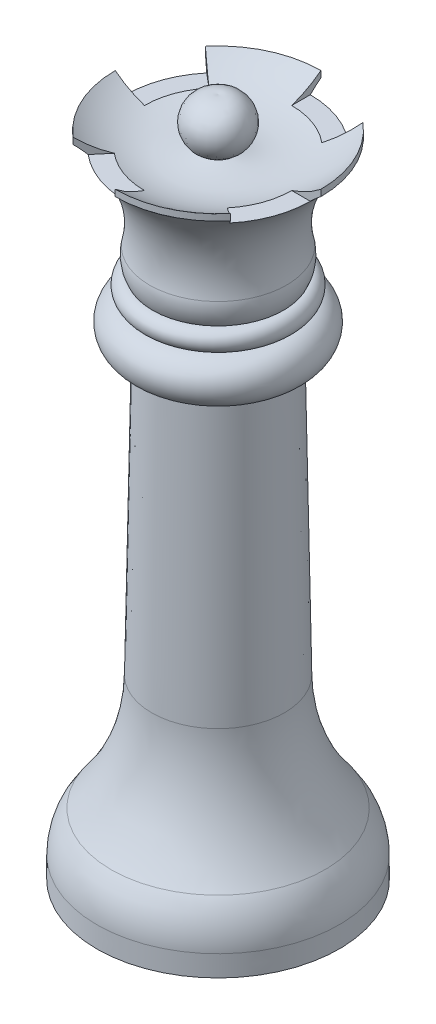
SolidWorks part; units mm, degrees
material "PVC Rigid"
ref_plane "Front Plane" through (0, 0, 0) normal (0, 0, 1) x (1, 0, 0)
ref_plane "Top Plane" through (0, 0, 0) normal (0, 1, 0) x (1, 0, 0)
ref_plane "Right Plane" through (0, 0, 0) normal (1, 0, 0) x (0, 0, -1)
sketch "Sketch1" plane through (0, 0, 0) normal (0, 0, 1) x (1, 0, 0)
  line L0 (0, 0) -> (-11.6, 0)
  line L3 (-11.5897, 2) -> (-11.6, 0)
  line L32 (0, 65) -> (0, 0)
  line L33 (-5.8734, 44.12) -> (-6.3432, 44.12)
  line L34 (-6.3432, 16.936) -> (-5.8734, 44.12)
  line L35 (-9.8373, 61.4466) -> (-9.8373, 62.061)
  line L36 (0, 0) -> (0, 50) construction
  arc A0 (-10.2296, 5.8838) -> (-11.5897, 2) centre (-5.271, 1.9673) ccw
  circle A32 centre (0, 62.5962) radius 2.4038 construction
  arc A34 (0, 65) -> (-1.2079, 60.5179) centre (-0.4218, 62.7099) ccw
  arc A36 (-6.3432, 44.12) -> (-6.2866, 48.2698) centre (-6.3432, 46.1953) cw
  arc A39 (-9.8373, 61.4466) -> (-6.5463, 52.467) centre (-15.0641, 54.4381) cw
  arc A40 (-10.2296, 5.8838) -> (-6.3432, 16.936) centre (-24.3998, 17.076) ccw
  arc A42 (-9.8373, 62.061) -> (-1.2079, 60.5179) centre (-4.0599, 69.4691) ccw
  arc A43 (-6.2866, 48.2698) -> (-6.2597, 50.24) centre (-6.2598, 49.2547) cw
  arc A44 (-6.5463, 52.467) -> (-6.2597, 50.24) centre (-3.4026, 51.7396) ccw
  dimension "D2" = 5.8734
  dimension "D6" = 4.1499
  dimension "D4" = 65
  dimension "D8" = 3.2268
  dimension "D9" = 8.7429
  dimension "D11" = 16.3979
  dimension "D13" = 20.88
  dimension "D15" = 17.941
  dimension "D16" = 2.0753
  dimension "D17" = 6.2866
  dimension "D19" = 8.3471
  dimension "D23" = 10.2296
  dimension "D21" = 5.8838
  dimension "D18" = 6.5463
  dimension "D20" = 9.3945
  dimension "D35" = 2.3287
  dimension "D7" = 0.9853
  dimension "D22" = 6.3187
  dimension "D1" = 2
  dimension "D5" = 11.6
  dimension "D10" = 0.6144
  dimension "D12" = 1.2079
  dimension "D14" = 8.6293
revolve "Revolve6" add sketch "Sketch1" angle 360 about L32 region at (-3.7198, 29.0748, 0)
sketch "Sketch10" plane through (0, 0, 0) normal (0, 0, 1) x (1, 0, 0)
  line L0 (-9.8373, 60.561) -> (-9.8373, 62.061) construction
  line L1 (-14.5937, 60.561) -> (-5.0809, 60.561)
  line L2 (-14.5937, 60.561) -> (-14.5937, 72.2832)
  line L3 (-14.5937, 72.2832) -> (-5.0809, 72.2832)
  line L4 (-5.0809, 60.561) -> (-5.0809, 72.2832)
  dimension "D1" = 1.5
revolve "Cut-Revolve8" cut sketch "Sketch10" angle 40 about L36 reverse direction yes
sketch "Sketch11" plane through (0, 0, 0) normal (0, 0, 1) x (1, 0, 0)
  line L0 (9.8373, 60.561) -> (9.8373, 62.061) construction
  line L1 (6.3584, 60.561) -> (13.3161, 60.561)
  line L2 (6.3584, 60.561) -> (6.3584, 71.1571)
  line L3 (6.3584, 71.1571) -> (13.3161, 71.1571)
  line L4 (13.3161, 60.561) -> (13.3161, 71.1571)
  line L5 (-9.8373, 62.061) -> (9.8373, 62.061) construction
  dimension "D1" = 1.5
revolve "Cut-Revolve9" cut sketch "Sketch11" angle 40 about L36 reverse direction yes
sketch "Sketch12" plane through (0, 0, 0) normal (1, 0, 0) x (0, 0, -1)
  line L0 (9.8373, 60.561) -> (9.8373, 62.061) construction
  line L1 (5.2356, 60.561) -> (14.4389, 60.561)
  line L2 (5.2356, 60.561) -> (5.2356, 72.223)
  line L3 (5.2356, 72.223) -> (14.4389, 72.223)
  line L4 (14.4389, 60.561) -> (14.4389, 72.223)
  line L5 (0, 62.061) -> (9.8373, 62.061) construction
  dimension "D1" = 1.5
revolve "Cut-Revolve10" cut sketch "Sketch12" angle 40 about L36 reverse direction yes
sketch "Sketch13" plane through (0, 0, 0) normal (1, 0, 0) x (0, 0, -1)
  line L0 (-9.8373, 60.561) -> (-9.8373, 62.061) construction
  line L1 (-14.1563, 60.561) -> (-5.5182, 60.561)
  line L2 (-14.1563, 60.561) -> (-14.1563, 72.4481)
  line L3 (-14.1563, 72.4481) -> (-5.5182, 72.4481)
  line L4 (-5.5182, 60.561) -> (-5.5182, 72.4481)
  line L5 (0, 62.061) -> (-9.8373, 62.061) construction
  dimension "D1" = 1.5
revolve "Cut-Revolve11" cut sketch "Sketch13" angle 40 about L36 reverse direction yes
sketch "Sketch8" plane through (0, 0, 0) normal (0, -1, 0) x (1, 0, 0)
  circle A0 centre (0, 0) radius 10
extrude "Cut-Extrude1" cut sketch "Sketch8" against normal blind 2.4 from offset 0.4 offset against normal yes
